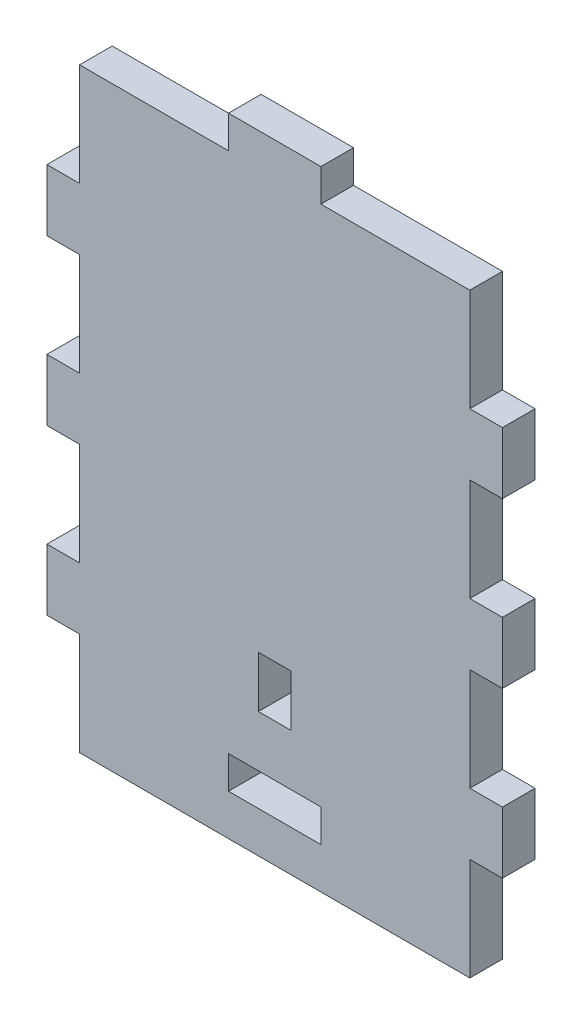
SolidWorks part; units mm, degrees
ref_plane "Front Plane" through (0, 0, 0) normal (0, 0, 1) x (1, 0, 0)
ref_plane "Top Plane" through (0, 0, 0) normal (0, 1, 0) x (1, 0, 0)
ref_plane "Right Plane" through (0, 0, 0) normal (1, 0, 0) x (0, 0, -1)
sketch "Sketch1" plane through (0, 0, 0) normal (0, 0, 1) x (1, 0, 0)
  line L0 (0, 0) -> (0, 10)
  line L1 (0, 10) -> (3.175, 10)
  line L2 (3.175, 10) -> (3.175, 16)
  line L3 (3.175, 16) -> (0, 16)
  line L4 (0, 16) -> (0, 26)
  line L5 (0, 26) -> (3.175, 26)
  line L6 (3.175, 26) -> (3.175, 32)
  line L7 (3.175, 32) -> (0, 32)
  line L8 (0, 32) -> (0, 42)
  line L9 (0, 42) -> (3.175, 42)
  line L10 (3.175, 42) -> (3.175, 48)
  line L11 (3.175, 48) -> (0, 48)
  line L12 (0, 48) -> (0, 58)
  line L13 (0, 58) -> (-14.5, 58)
  line L14 (-14.5, 58) -> (-14.5, 61.175)
  line L15 (-14.5, 61.175) -> (-23.5, 61.175)
  line L16 (-23.5, 61.175) -> (-23.5, 58)
  line L17 (-23.5, 58) -> (-38, 58)
  line L18 (3.175, 29) -> (-38.4558, 29) construction
  line L19 (-19, 61.175) -> (-19, 29) construction
  line L20 (-38, 48) -> (-38, 58)
  line L21 (-41.175, 48) -> (-38, 48)
  line L22 (-41.175, 42) -> (-41.175, 48)
  line L23 (-38, 42) -> (-41.175, 42)
  line L24 (-38, 32) -> (-38, 42)
  line L25 (-41.175, 32) -> (-38, 32)
  line L26 (-41.175, 26) -> (-41.175, 32)
  line L27 (-38, 26) -> (-41.175, 26)
  line L28 (-38, 16) -> (-38, 26)
  line L29 (-41.175, 16) -> (-38, 16)
  line L30 (-41.175, 10) -> (-41.175, 16)
  line L31 (-38, 10) -> (-41.175, 10)
  line L32 (-38, 0) -> (-38, 10)
  line L33 (-38, 0) -> (0, 0)
  line L34 (-19, 0) -> (-19, 4)
  line L35 (-14.5, 4) -> (-14.5, 7.175)
  line L36 (-14.5, 7.175) -> (-23.5, 7.175)
  line L37 (-14.5, 4) -> (-23.5, 4)
  line L38 (-23.5, 4) -> (-23.5, 7.175)
  line L39 (-19, 12.175) -> (-19, 7.175)
  line L40 (-19, 12.175) -> (-17.4125, 12.175)
  line L41 (-17.4125, 12.175) -> (-17.4125, 17.175)
  line L42 (-17.4125, 17.175) -> (-20.5875, 17.175)
  line L43 (-20.5875, 17.175) -> (-20.5875, 12.175)
  line L44 (-20.5875, 12.175) -> (-19, 12.175)
  point P44 (-19, 7.175)
  dimension "D1" = 4
  dimension "D2" = 3.175
  dimension "D3" = 6
  dimension "D4" = 10
  dimension "D5" = 9
  dimension "D6" = 3.175
  dimension "D7" = 38
  dimension "D8" = 3.175
  dimension "D9" = 9
  dimension "D10" = 5
  dimension "D11" = 3.175
  dimension "D12" = 5
extrude "Boss-Extrude2" add sketch "Sketch1" along normal mid plane 3.175 contours L44 L43 L42 L41 L40 L36 L35 L37 L33 L0 L1 L2 L3 L4 L5 L6 L7 L8 L9 L10 L11 L12 L13 L14 L15 L16 L17 L20 L21 L22 L23 L24 L25 L26 L27 L28 L29 L30 L31 L32 L38 region at (-19, 29.769, 0)
